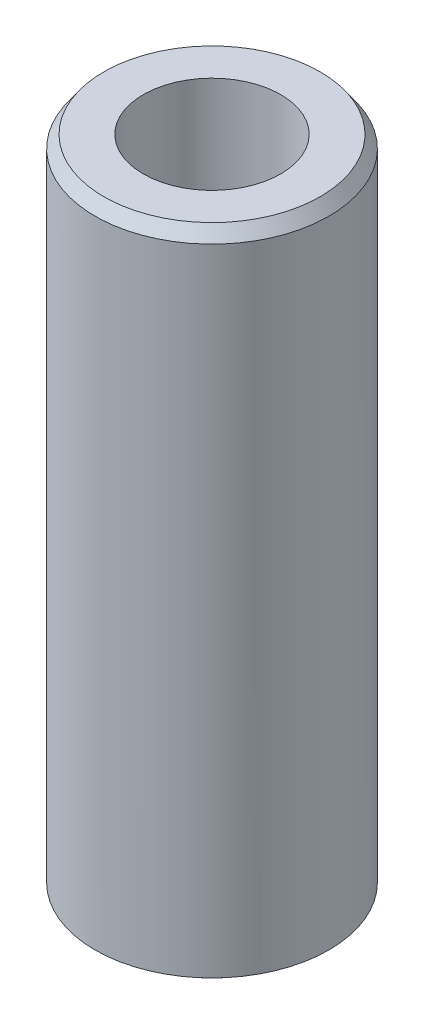
SolidWorks part; units mm, degrees
ref_plane "Front Plane" through (0, 0, 0) normal (0, 0, 1) x (1, 0, 0)
ref_plane "Top Plane" through (0, 0, 0) normal (0, 1, 0) x (1, 0, 0)
ref_plane "Right Plane" through (0, 0, 0) normal (1, 0, 0) x (0, 0, -1)
sketch "Sketch1" plane through (0, 0, 0) normal (0, 1, 0) x (1, 0, 0)
  circle A0 centre (0, 0) radius 17.5
  dimension "SHAFT_OD" = 35
extrude "Boss-Extrude1" add sketch "Sketch1" along normal blind 98.253
sketch "Sketch2" plane through (0, 0, 0) normal (0, 1, 0) x (1, 0, 0)
  circle A0 centre (0, 0) radius 10.2835
  dimension "BORE_D" = 20.5669
extrude "Cut-Extrude1" cut sketch "Sketch2" along normal through all
chamfer "Chamfer1" distance 1.8639 angle 35.183 2 edges at (0, 98.253, 17.5) (0, 0, 17.5) first distance on face at (0, 98.253, 17.5) first distance on face at (0, 0, 10.2835)
